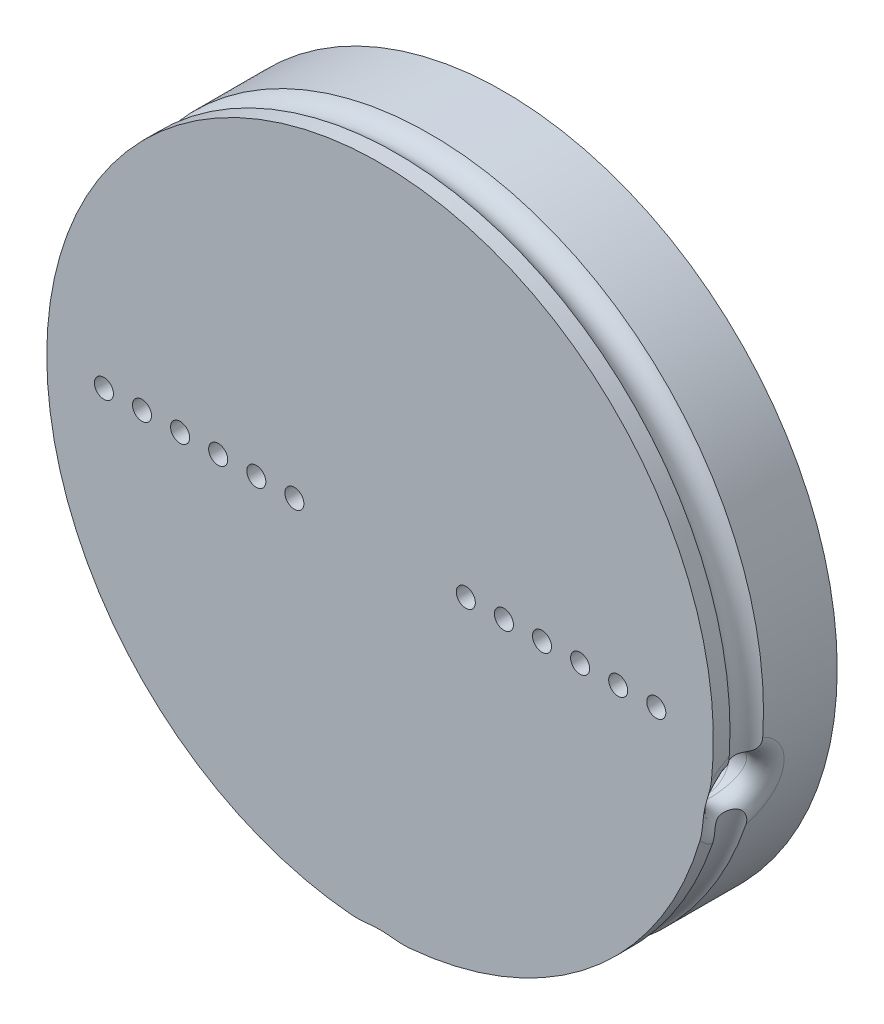
SolidWorks part; units mm, degrees
ref_plane "Front Plane" through (0, 0, 0) normal (0, 0, 1) x (1, 0, 0)
ref_plane "Top Plane" through (0, 0, 0) normal (0, 1, 0) x (1, 0, 0)
ref_plane "Right Plane" through (0, 0, 0) normal (1, 0, 0) x (0, 0, -1)
sketch "Sketch1" plane through (0, 0, 0) normal (0, 0, 1) x (1, 0, 0)
  line L0 (16, 0) -> (-16, 0) construction
  line L1 (1.8028, 3) -> (13.8853, 2.25)
  line L2 (1.8028, -3) -> (13.8853, -2.25)
  line L3 (-1.8028, 3) -> (-13.8853, 2.25)
  line L4 (-1.8028, -3) -> (-13.8853, -2.25)
  circle A1 centre (0, 0) radius 17.5
  circle A2 centre (0, 0) radius 3.5
  arc A3 (13.8853, 2.25) -> (13.8853, -2.25) centre (13.7457, 0) cw
  arc A4 (-13.8853, 2.25) -> (-13.8853, -2.25) centre (-13.7457, 0) ccw
  point P6 (0, 0)
  dimension "D1" = 35
  dimension "D3" = 7
  dimension "D2" = 32
  dimension "D4" = 6
  dimension "D5" = 4.5
extrude "Boss-Extrude1" add sketch "Sketch1" along normal blind 2.5 contours A1 A4 L3 A2 L1 A3 L2 L4 region at (-17.005, 0, 0)
sketch "Sketch2" plane through (0, 0, 2.5) normal (0, 0, 1) x (1, 0, 0)
  circle A0 centre (0, 0) radius 17.5 construction
  circle A1 centre (0, 0) radius 17.5
extrude "Boss-Extrude2" add sketch "Sketch2" along normal blind 4
ref_plane "Plane1" through (0, 0, 4.75) normal (0, 0, 1) x (1, 0, 0)
sketch "Sketch3" plane through (0, 0, 4.75) normal (0, 0, 1) x (1, 0, 0)
  line L0 (0, -19.3296) -> (0, -16.6112)
  line L1 (0, -4.125) -> (0, 4.125) construction
  line L2 (15.3583, -3.2049) -> (21.6443, -3.2049)
  arc A0 (0, -16.6112) -> (3.6696, -12.7593) centre (3.8564, -16.6112) cw
  arc A1 (3.6696, -12.7593) -> (10.8634, -6.7677) centre (3.2928, -4.9926) ccw
  arc A2 (10.8634, -6.7677) -> (15.3583, -3.2049) centre (15.3583, -7.8217) cw
ref_plane "Plane2" through (0, -17.5, 0) normal (0, -1, 0) x (-1, 0, 0)
sketch "Sketch4" plane through (0, -17.5, 0) normal (0, -1, 0) x (-1, 0, 0)
  circle A0 centre (0, -4.75) radius 1.25
  dimension "D1" = 2.5
sweep "Cut-Sweep1" cut profiles "Sketch4" path "Sketch3"
sketch "Sketch6" plane through (0, 0, 0) normal (0, 0, -1) x (-1, 0, 0)
  line L0 (1.8028, 3) -> (13.8853, 2.25) construction
  line L1 (1.8028, -3) -> (13.8853, -2.25) construction
  line L2 (-1.8028, 3) -> (-13.8853, 2.25) construction
  line L3 (-1.8028, -3) -> (-13.8853, -2.25) construction
  line L4 (1.8028, 3) -> (13.8853, 2.25) construction
  line L5 (1.8028, -3) -> (13.8853, -2.25) construction
  line L6 (-1.8028, 3) -> (-13.8853, 2.25) construction
  line L7 (-1.8028, -3) -> (-13.8853, -2.25) construction
  line L8 (-16, 0) -> (16, 0) construction
  arc A0 (13.8853, -2.25) -> (13.8853, 2.25) centre (13.7457, 0) ccw construction
  circle A1 centre (0, 0) radius 3.5
  circle A2 centre (0, 0) radius 3.5 construction
  circle A3 centre (0, 0) radius 17.5
  circle A4 centre (0, 0) radius 17.5 construction
  arc A5 (-13.8853, 2.25) -> (-13.8853, -2.25) centre (-13.7457, 0) ccw construction
  arc A6 (13.8853, -2.25) -> (13.8853, 2.25) centre (13.7457, 0) ccw construction
  arc A7 (-13.8853, 2.25) -> (-13.8853, -2.25) centre (-13.7457, 0) ccw construction
  circle A8 centre (-14.5, 0) radius 0.5
  circle A9 centre (-12.5, 0) radius 0.5
  circle A10 centre (-10.5, 0) radius 0.5
  circle A11 centre (-8.5, 0) radius 0.5
  circle A12 centre (-6.5, 0) radius 0.5
  circle A13 centre (-4.5, 0) radius 0.5
  circle A14 centre (14.5, 0) radius 0.5
  circle A15 centre (12.5, 0) radius 0.5
  circle A16 centre (10.5, 0) radius 0.5
  circle A17 centre (8.5, 0) radius 0.5
  circle A18 centre (6.5, 0) radius 0.5
  circle A19 centre (4.5, 0) radius 0.5
  dimension "D5" = 1
  dimension "D6" = 1
  dimension "D3" = 1.5
  dimension "D7" = 1.5
  dimension "D1" = 0
  dimension "D2" = 0
  dimension "D4" = 6
  dimension "D8" = 6
extrude "Cut-Extrude1" cut sketch "Sketch6" against normal through all
fillet "Fillet1" radius 1 2 edges at (17.1492, -3.4863, 3.5321) (0.2839, -17.4977, 5.9673)
sketch "Sketch7" plane through (0, 0, 4.75) normal (0, 0, 1) x (1, 0, 0)
  circle A0 centre (0, 0) radius 17.9686
sketch "Sketch8" plane through (0, 0, 0) normal (0, 1, 0) x (1, 0, 0)
  circle A0 centre (-17.9686, -4.75) radius 0.9964
  point P2 (0, 0)
sweep "Cut-Sweep2" cut profiles "Sketch8" path "Sketch7"
